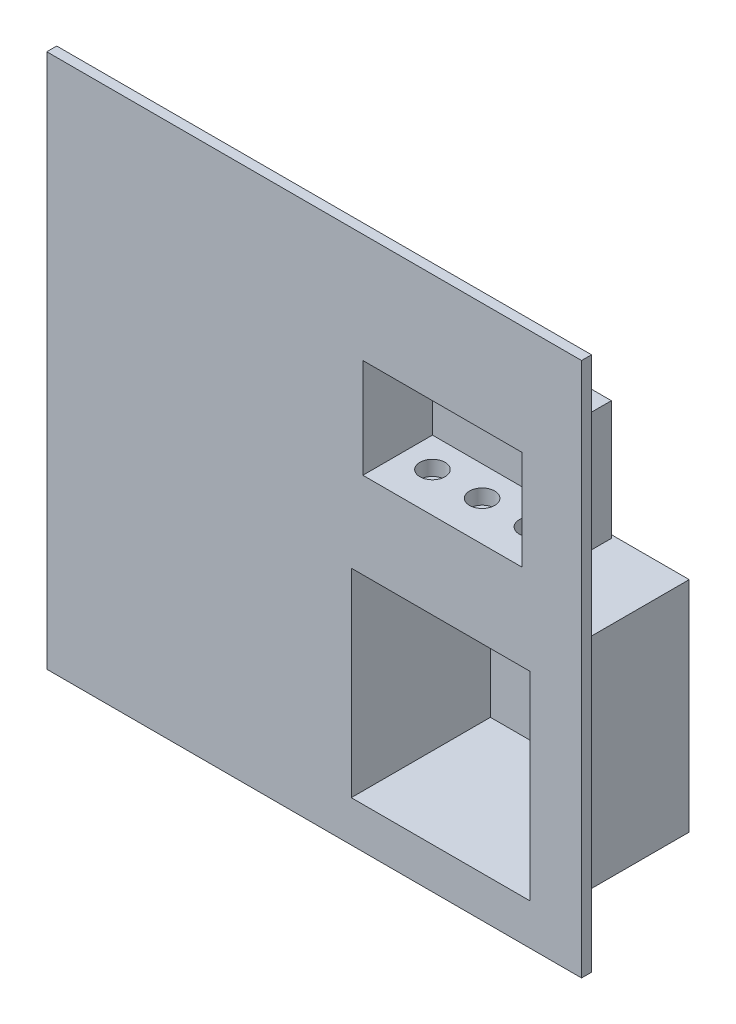
SolidWorks part; units mm, degrees
material "PE High Density Film"
ref_plane "Front Plane" through (0, 0, 0) normal (0, 0, 1) x (1, 0, 0)
ref_plane "Top Plane" through (0, 0, 0) normal (0, 1, 0) x (1, 0, 0)
ref_plane "Right Plane" through (0, 0, 0) normal (1, 0, 0) x (0, 0, -1)
sketch "Sketch1" plane through (0, 0, 0) normal (0, 0, 1) x (1, 0, 0)
  line L1 (0, 0) -> (683.26, 0)
  line L2 (0, 0) -> (0, 683.26)
  line L3 (0, 683.26) -> (683.26, 683.26)
  line L4 (683.26, 0) -> (683.26, 683.26)
  line L5 (403.86, 543.56) -> (607.06, 543.56)
  line L6 (403.86, 543.56) -> (403.86, 416.56)
  line L7 (403.86, 416.56) -> (607.06, 416.56)
  line L8 (607.06, 543.56) -> (607.06, 416.56)
  point P9 (607.06, 480.06)
  dimension "D1" = 683.26
  dimension "D2" = 76.2
  dimension "D3" = 203.2
  dimension "D4" = 127
  dimension "D5" = 203.2
extrude "Boss-Extrude1" add sketch "Sketch1" along normal blind 12.7
sketch "Sketch2" plane through (0, 416.56, 0) normal (0, 1, 0) x (1, 0, 0)
  line L1 (403.86, 0) -> (607.06, 0)
  line L2 (403.86, 0) -> (403.86, 76.2)
  line L3 (403.86, 76.2) -> (607.06, 76.2)
  line L4 (607.06, 0) -> (607.06, 76.2)
  dimension "D1" = 76.2
extrude "Boss-Extrude2" add sketch "Sketch2" against normal blind 25.4
sketch "Sketch3" plane through (0, 416.56, 0) normal (0, 1, 0) x (1, 0, 0)
  line L6 (607.06, -12.7) -> (607.06, 0)
  line L7 (607.06, 0) -> (607.06, 76.2)
  line L8 (607.06, 76.2) -> (403.86, 76.2)
  line L9 (403.86, 76.2) -> (403.86, 0)
  line L10 (403.86, 0) -> (403.86, -12.7)
  line L11 (403.86, -12.7) -> (607.06, -12.7)
  line L12 (607.06, -12.7) -> (607.06, 0)
  line L13 (607.06, 0) -> (607.06, 76.2)
  line L14 (607.06, 76.2) -> (403.86, 76.2)
  line L15 (403.86, 76.2) -> (403.86, 0)
  line L16 (403.86, 0) -> (403.86, -12.7)
  line L17 (403.86, -12.7) -> (607.06, -12.7)
  circle A1 centre (441.96, 38.1) radius 16.0655
  circle A2 centre (505.46, 38.1) radius 16.0655
  circle A3 centre (568.96, 38.1) radius 16.0655
  point P6 (403.86, 38.1)
  dimension "D2" = 32.131
  dimension "D4" = 32.131
  dimension "D5" = 32.131
  dimension "D3" = 38.1
  dimension "D6" = 63.5
  dimension "D7" = 63.5
  dimension "D1" = 0
extrude "Cut-Extrude1" cut sketch "Sketch3" against normal blind 19.05 contours A3 | A2 | A1 region at (441.96, 416.56, -38.1) region at (505.46, 416.56, -38.1) region at (568.96, 416.56, -38.1)
sketch "Sketch4" plane through (0, 0, 0) normal (0, 0, -1) x (-1, 0, 0)
  line L0 (-607.06, 416.56) -> (-403.86, 416.56) construction
  line L1 (-607.06, 416.56) -> (-619.76, 416.56)
  line L2 (-607.06, 416.56) -> (-607.06, 543.56)
  line L3 (-607.06, 543.56) -> (-619.76, 543.56)
  line L4 (-619.76, 416.56) -> (-619.76, 543.56)
  line L5 (-607.06, 543.56) -> (-403.86, 543.56)
  line L6 (-607.06, 543.56) -> (-607.06, 556.26)
  line L7 (-607.06, 556.26) -> (-403.86, 556.26)
  line L8 (-403.86, 543.56) -> (-403.86, 556.26)
  line L9 (-403.86, 543.56) -> (-391.16, 543.56)
  line L10 (-403.86, 543.56) -> (-403.86, 416.56)
  line L11 (-403.86, 416.56) -> (-391.16, 416.56)
  line L12 (-391.16, 543.56) -> (-391.16, 416.56)
  line L13 (-403.86, 543.56) -> (-403.86, 416.56) construction
  line L15 (-607.06, 543.56) -> (-403.86, 543.56) construction
  line L16 (-607.06, 543.56) -> (-619.76, 543.56)
  line L17 (-607.06, 543.56) -> (-607.06, 556.26)
  line L18 (-607.06, 556.26) -> (-619.76, 556.26)
  line L19 (-619.76, 543.56) -> (-619.76, 556.26)
  line L20 (-403.86, 543.56) -> (-391.16, 543.56)
  line L21 (-403.86, 543.56) -> (-403.86, 556.26)
  line L22 (-403.86, 556.26) -> (-391.16, 556.26)
  line L23 (-391.16, 543.56) -> (-391.16, 556.26)
  line L24 (-607.06, 416.56) -> (-619.76, 416.56)
  line L25 (-607.06, 416.56) -> (-607.06, 403.86)
  line L26 (-607.06, 403.86) -> (-619.76, 403.86)
  line L27 (-619.76, 416.56) -> (-619.76, 403.86)
  line L28 (-403.86, 416.56) -> (-391.16, 416.56)
  line L29 (-403.86, 416.56) -> (-403.86, 403.86)
  line L30 (-403.86, 403.86) -> (-391.16, 403.86)
  line L31 (-391.16, 416.56) -> (-391.16, 403.86)
  line M7 (-403.86, 416.56) -> (-403.86, 391.16)
  line M9 (-607.06, 391.16) -> (-607.06, 416.56)
  line M10 (-607.06, 416.56) -> (-607.06, 543.56)
  line M11 (-607.06, 543.56) -> (-403.86, 543.56)
  line M12 (-403.86, 543.56) -> (-403.86, 416.56)
  dimension "D1" = 12.7
  dimension "D2" = 12.7
  dimension "D3" = 12.7
extrude "Boss-Extrude4" add sketch "Sketch4" along normal up to surface (76.2 mm away) contours L1 L27 L26 M9 | L4 L1 L3 M10 | L8 L7 L6 M11 | L19 L3 L6 L18 | L9 L23 L22 L8 | L12 L9 L11 M12 | L31 L11 L30 M7 region at (613.41, 410.21, 0) region at (613.41, 480.06, 0) region at (505.46, 549.91, 0) region at (613.41, 549.91, 0) region at (397.51, 549.91, 0) region at (397.51, 480.06, 0) region at (397.51, 410.21, 0) up to face at (505.46, 403.86, -76.2)
sketch "Sketch5" plane through (0, 0, -76.2) normal (0, 0, -1) x (-1, 0, 0)
  line L4 (-607.06, 391.16) -> (-403.86, 391.16)
  line L5 (-391.16, 403.86) -> (-391.16, 556.26)
  line L6 (-391.16, 556.26) -> (-619.76, 556.26)
  line L7 (-619.76, 556.26) -> (-619.76, 403.86)
  line L8 (-607.06, 391.16) -> (-403.86, 391.16)
  line L9 (-391.16, 403.86) -> (-391.16, 556.26)
  line L10 (-391.16, 556.26) -> (-619.76, 556.26)
  line L11 (-619.76, 556.26) -> (-619.76, 403.86)
  line L16 (-403.86, 391.16) -> (-403.86, 403.86)
  line L17 (-403.86, 391.16) -> (-403.86, 403.86)
  line L18 (-403.86, 403.86) -> (-391.16, 403.86)
  line L19 (-403.86, 403.86) -> (-391.16, 403.86)
  line L20 (-619.76, 403.86) -> (-607.06, 403.86)
  line L21 (-619.76, 403.86) -> (-607.06, 403.86)
  line L22 (-607.06, 403.86) -> (-607.06, 391.16)
  line L23 (-607.06, 403.86) -> (-607.06, 391.16)
  dimension "D1" = 0
extrude "Boss-Extrude5" add sketch "Sketch5" along normal blind 12.7
sketch "Sketch6" plane through (0, 0, 12.7) normal (0, 0, 1) x (1, 0, 0)
  line L1 (389.0156, 306.3991) -> (617.6156, 306.3991)
  line L2 (389.0156, 306.3991) -> (389.0156, 52.3991)
  line L3 (389.0156, 52.3991) -> (617.6156, 52.3991)
  line L4 (617.6156, 306.3991) -> (617.6156, 52.3991)
  dimension "D1" = 254
  dimension "D2" = 228.6
extrude "Cut-Extrude2" cut sketch "Sketch6" against normal through all
sketch "Sketch7" plane through (0, 0, 0) normal (0, 0, -1) x (-1, 0, 0)
  line L1 (-617.6156, 52.3991) -> (-389.0156, 52.3991)
  line L2 (-617.6156, 52.3991) -> (-617.6156, 39.6991)
  line L3 (-617.6156, 39.6991) -> (-389.0156, 39.6991)
  line L4 (-389.0156, 52.3991) -> (-389.0156, 39.6991)
  dimension "D1" = 12.7
extrude "Boss-Extrude6" add sketch "Sketch7" along normal blind 177.8
ref_plane "Plane1" through (0, 179.3991, 0) normal (0, 1, 0) x (1, 0, 0)
mirror "Mirror1" about plane through (0, 179.3991, 0) normal (0, 1, 0) of "Boss-Extrude6"
sketch "Sketch8" plane through (0, 0, 0) normal (0, 0, -1) x (-1, 0, 0)
  line L5 (-617.6156, 319.0991) -> (-630.3156, 319.0991)
  line L6 (-617.6156, 319.0991) -> (-617.6156, 39.6991)
  line L7 (-617.6156, 39.6991) -> (-630.3156, 39.6991)
  line L8 (-630.3156, 319.0991) -> (-630.3156, 39.6991)
  line L9 (-389.0156, 319.0991) -> (-376.3156, 319.0991)
  line L10 (-389.0156, 319.0991) -> (-389.0156, 39.6991)
  line L11 (-389.0156, 39.6991) -> (-376.3156, 39.6991)
  line L12 (-376.3156, 319.0991) -> (-376.3156, 39.6991)
  dimension "D1" = 12.7
  dimension "D2" = 279.4
  dimension "D3" = 12.7
  dimension "D4" = 279.4
extrude "Boss-Extrude7" add sketch "Sketch8" along normal blind 177.8
sketch "Sketch9" plane through (0, 52.3991, 0) normal (0, 1, 0) x (1, 0, 0)
  line L0 (617.6156, 177.8) -> (617.6156, -12.7) construction
  line L1 (389.0156, 177.8) -> (617.6156, 177.8)
  line L2 (389.0156, 177.8) -> (389.0156, 165.1)
  line L3 (389.0156, 165.1) -> (617.6156, 165.1)
  line L4 (617.6156, 177.8) -> (617.6156, 165.1)
  dimension "D1" = 12.7
extrude "Boss-Extrude8" add sketch "Sketch9" along normal blind 254
